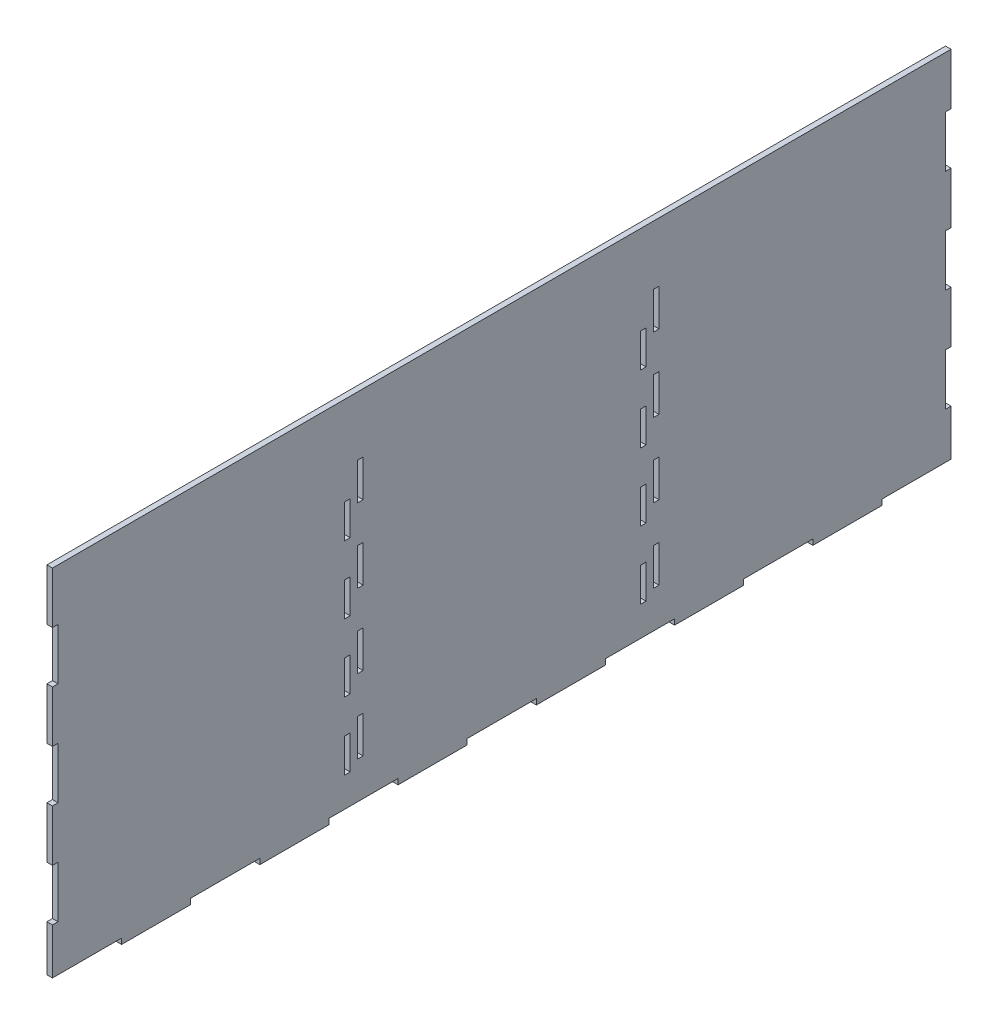
SolidWorks part; units mm, degrees
ref_plane "Front Plane" through (0, 0, 0) normal (0, 0, 1) x (1, 0, 0)
ref_plane "Top Plane" through (0, 0, 0) normal (0, 1, 0) x (1, 0, 0)
ref_plane "Right Plane" through (0, 0, 0) normal (1, 0, 0) x (0, 0, -1)
sketch "Sketch1" plane through (0, 0, 0) normal (1, 0, 0) x (0, 0, -1)
  line L0 (0, 152.4) -> (0, -152.4) construction
  line L1 (-381, 152.4) -> (381, 152.4)
  line L2 (-381, 152.4) -> (-381, -152.4)
  line L3 (-381, -152.4) -> (381, -152.4)
  line L4 (381, 152.4) -> (381, -152.4)
  line L5 (-381, 108.1768) -> (-381, 63.9536)
  line L10 (-381, 152.4) -> (-385.7625, 152.4)
  line L11 (-381, 152.4) -> (-381, 108.1768)
  line L12 (-381, 108.1768) -> (-385.7625, 108.1768)
  line L13 (-385.7625, 152.4) -> (-385.7625, 108.1768)
  line L14 (381, 152.4) -> (385.7625, 152.4)
  line L15 (381, 152.4) -> (381, 108.1768)
  line L16 (381, 108.1768) -> (385.7625, 108.1768)
  line L17 (385.7625, 152.4) -> (385.7625, 108.1768)
  line L18 (-385.7625, -152.4) -> (-326.4144, -152.4)
  line L19 (-385.7625, -152.4) -> (-385.7625, -157.1625)
  line L20 (-385.7625, -157.1625) -> (-326.4144, -157.1625)
  line L21 (-326.4144, -152.4) -> (-326.4144, -157.1625)
  line L22 (-381, 108.1768) -> (-385.7625, 108.1768)
  line L23 (-385.7625, 108.1768) -> (-385.7625, 63.9536)
  line L24 (-381, 63.9536) -> (-385.7625, 63.9536)
  line L25 (381, 108.1768) -> (381, 63.9536)
  line L26 (381, 108.1768) -> (385.7625, 108.1768)
  line L27 (385.7625, 108.1768) -> (385.7625, 63.9536)
  line L28 (381, 63.9536) -> (385.7625, 63.9536)
  line L29 (-381, 63.9536) -> (-381, 19.7304)
  line L30 (-381, 63.9536) -> (-385.7625, 63.9536)
  line L31 (-385.7625, 63.9536) -> (-385.7625, 19.7304)
  line L32 (-381, 19.7304) -> (-385.7625, 19.7304)
  line L33 (381, 63.9536) -> (381, 19.7304)
  line L34 (381, 63.9536) -> (385.7625, 63.9536)
  line L35 (385.7625, 63.9536) -> (385.7625, 19.7304)
  line L36 (381, 19.7304) -> (385.7625, 19.7304)
  line L37 (-381, 19.7304) -> (-381, -24.4929)
  line L38 (-381, 19.7304) -> (-385.7625, 19.7304)
  line L39 (-385.7625, 19.7304) -> (-385.7625, -24.4929)
  line L40 (-381, -24.4929) -> (-385.7625, -24.4929)
  line L41 (381, 19.7304) -> (381, -24.4929)
  line L42 (381, 19.7304) -> (385.7625, 19.7304)
  line L43 (385.7625, 19.7304) -> (385.7625, -24.4929)
  line L44 (381, -24.4929) -> (385.7625, -24.4929)
  line L45 (-381, -24.4929) -> (-381, -68.7161)
  line L46 (-381, -24.4929) -> (-385.7625, -24.4929)
  line L47 (-385.7625, -24.4929) -> (-385.7625, -68.7161)
  line L48 (-381, -68.7161) -> (-385.7625, -68.7161)
  line L49 (381, -24.4929) -> (381, -68.7161)
  line L50 (381, -24.4929) -> (385.7625, -24.4929)
  line L51 (385.7625, -24.4929) -> (385.7625, -68.7161)
  line L52 (381, -68.7161) -> (385.7625, -68.7161)
  line L53 (-381, -68.7161) -> (-381, -112.9393)
  line L54 (-381, -68.7161) -> (-385.7625, -68.7161)
  line L55 (-385.7625, -68.7161) -> (-385.7625, -112.9393)
  line L56 (-381, -112.9393) -> (-385.7625, -112.9393)
  line L57 (381, -68.7161) -> (381, -112.9393)
  line L58 (381, -68.7161) -> (385.7625, -68.7161)
  line L59 (385.7625, -68.7161) -> (385.7625, -112.9393)
  line L60 (381, -112.9393) -> (385.7625, -112.9393)
  line L61 (-381, -112.9393) -> (-381, -157.1625)
  line L62 (-381, -112.9393) -> (-385.7625, -112.9393)
  line L63 (-385.7625, -112.9393) -> (-385.7625, -157.1625)
  line L64 (-381, -157.1625) -> (-385.7625, -157.1625)
  line L65 (381, -112.9393) -> (381, -157.1625)
  line L66 (381, -112.9393) -> (385.7625, -112.9393)
  line L67 (385.7625, -112.9393) -> (385.7625, -157.1625)
  line L68 (381, -157.1625) -> (385.7625, -157.1625)
  line L69 (-326.4144, -157.1625) -> (-267.0663, -157.1625)
  line L70 (-326.4144, -152.4) -> (-326.4144, -157.1625)
  line L71 (-326.4144, -152.4) -> (-267.0663, -152.4)
  line L72 (-267.0663, -152.4) -> (-267.0663, -157.1625)
  line L73 (-267.0663, -157.1625) -> (-207.7183, -157.1625)
  line L74 (-267.0663, -152.4) -> (-267.0663, -157.1625)
  line L75 (-267.0663, -152.4) -> (-207.7183, -152.4)
  line L76 (-207.7183, -152.4) -> (-207.7183, -157.1625)
  line L77 (-207.7183, -157.1625) -> (-148.3702, -157.1625)
  line L78 (-207.7183, -152.4) -> (-207.7183, -157.1625)
  line L79 (-207.7183, -152.4) -> (-148.3702, -152.4)
  line L80 (-148.3702, -152.4) -> (-148.3702, -157.1625)
  line L81 (-148.3702, -157.1625) -> (-89.0221, -157.1625)
  line L82 (-148.3702, -152.4) -> (-148.3702, -157.1625)
  line L83 (-148.3702, -152.4) -> (-89.0221, -152.4)
  line L84 (-89.0221, -152.4) -> (-89.0221, -157.1625)
  line L85 (-89.0221, -157.1625) -> (-29.674, -157.1625)
  line L86 (-89.0221, -152.4) -> (-89.0221, -157.1625)
  line L87 (-89.0221, -152.4) -> (-29.674, -152.4)
  line L88 (-29.674, -152.4) -> (-29.674, -157.1625)
  line L89 (-29.674, -157.1625) -> (29.674, -157.1625)
  line L90 (-29.674, -152.4) -> (-29.674, -157.1625)
  line L91 (-29.674, -152.4) -> (29.674, -152.4)
  line L92 (29.674, -152.4) -> (29.674, -157.1625)
  line L93 (29.674, -157.1625) -> (89.0221, -157.1625)
  line L94 (29.674, -152.4) -> (29.674, -157.1625)
  line L95 (29.674, -152.4) -> (89.0221, -152.4)
  line L96 (89.0221, -152.4) -> (89.0221, -157.1625)
  line L97 (89.0221, -157.1625) -> (148.3702, -157.1625)
  line L98 (89.0221, -152.4) -> (89.0221, -157.1625)
  line L99 (89.0221, -152.4) -> (148.3702, -152.4)
  line L100 (148.3702, -152.4) -> (148.3702, -157.1625)
  line L101 (148.3702, -157.1625) -> (207.7183, -157.1625)
  line L102 (148.3702, -152.4) -> (148.3702, -157.1625)
  line L103 (148.3702, -152.4) -> (207.7183, -152.4)
  line L104 (207.7183, -152.4) -> (207.7183, -157.1625)
  line L105 (207.7183, -157.1625) -> (267.0663, -157.1625)
  line L106 (207.7183, -152.4) -> (207.7183, -157.1625)
  line L107 (207.7183, -152.4) -> (267.0663, -152.4)
  line L108 (267.0663, -152.4) -> (267.0663, -157.1625)
  line L125 (-124.6188, 0) -> (124.6188, 0) construction
  line L126 (-129.3812, 41.956) -> (-124.6188, 41.956) construction
  line L127 (-129.3812, 41.956) -> (-129.3812, -41.956) construction
  line L128 (-129.3812, -41.956) -> (-124.6188, -41.956) construction
  line L129 (-124.6188, 41.956) -> (-124.6188, -41.956) construction
  line L138 (124.6188, 41.956) -> (129.3813, 41.956) construction
  line L139 (124.6188, 41.956) -> (124.6188, -41.956) construction
  line L140 (124.6188, -41.956) -> (129.3813, -41.956) construction
  line L141 (129.3813, 41.956) -> (129.3813, -41.956) construction
  line L143 (267.0663, -157.1625) -> (326.4144, -157.1625)
  line L144 (267.0663, -152.4) -> (267.0663, -157.1625)
  line L145 (267.0663, -152.4) -> (326.4144, -152.4)
  line L146 (326.4144, -152.4) -> (326.4144, -157.1625)
  line L147 (326.4144, -157.1625) -> (385.7625, -157.1625)
  line L148 (326.4144, -152.4) -> (326.4144, -157.1625)
  line L149 (326.4144, -152.4) -> (385.7625, -152.4)
  line L150 (385.7625, -152.4) -> (385.7625, -157.1625)
  point P6 (0, 0)
  point P113 (-127, 41.956)
  point P114 (127, 41.956)
  point P117 (0, 0)
  dimension "D1" = 762
  dimension "D2" = 304.8
  dimension "D3" = 771.525
  dimension "D4" = 309.5625
  dimension "D5" = 44.2232
  dimension "D7" = 59.3481
  dimension "D9" = 254
  dimension "D10" = 4.7625
  dimension "D6" = 7
  dimension "D8" = 13
extrude "Boss-Extrude1" add sketch "Sketch1" along normal blind 4.7625 contours L0 L1 L2 L3 | L10 L13 L12 L2 | L32 L2 L24 L31 | L48 L2 L40 L47 | L56 L63 L18 L2 | L72 L3 L21 L69 | L80 L3 L76 L77 | L96 L3 L92 L93 | L3 L108 | L4 L67 L60 | L4 L52 L51 L44 | L4 L36 L35 L28 | L17 L14 L4 L16 | L88 L3 L84 L85 | L104 L3 L100 L101 region at (0, 0, 0) region at (0, 130.2884, 383.3813) region at (0, 130.2884, -383.3812) region at (0, 41.842, 383.3812) region at (0, 41.842, -383.3813) region at (0, -46.6045, 383.3812) region at (0, -46.6045, -383.3813) region at (0, -132.6696, 383.3812) region at (0, -132.6696, -383.3813) region at (0, -154.7813, 296.7404) region at (0, -154.7813, -296.7404) region at (0, -154.7813, 178.0442) region at (0, -154.7813, -178.0442) region at (0, -154.7813, 59.3481) region at (0, -154.7813, -59.3481)
sketch "Sketch3" plane through (4.7625, 0, 0) normal (1, 0, 0) x (0, 0, -1)
  line L0 (-130.175, -127) -> (-130.175, 76.2) construction
  line L5 (-134.9375, 76.2) -> (-130.175, 76.2)
  line L6 (-134.9375, 76.2) -> (-134.9375, 47.1714)
  line L7 (-134.9375, 47.1714) -> (-130.175, 47.1714)
  line L8 (-130.175, 76.2) -> (-130.175, 47.1714)
  line L9 (-119.0625, 101.6) -> (-123.825, 101.6)
  line L10 (-119.0625, 101.6) -> (-119.0625, 69.85)
  line L11 (-119.0625, 69.85) -> (-123.825, 69.85)
  line L12 (-123.825, 101.6) -> (-123.825, 69.85)
  line L13 (-381, -152.4) -> (381, -152.4) construction
  line L14 (-123.825, -152.4) -> (-123.825, 101.6) construction
  line L15 (-130.175, 76.2) -> (-123.825, 76.2) construction
  line L16 (-127, 41.956) -> (-127, 76.2) construction
  line L17 (-129.3812, 41.956) -> (-124.6188, 41.956) construction
  line L18 (-119.0625, 69.85) -> (-119.0625, 38.1)
  line L19 (-119.0625, 69.85) -> (-123.825, 69.85)
  line L20 (-123.825, 69.85) -> (-123.825, 38.1)
  line L21 (-119.0625, 38.1) -> (-123.825, 38.1)
  line L22 (-119.0625, 38.1) -> (-119.0625, 6.35)
  line L23 (-119.0625, 38.1) -> (-123.825, 38.1)
  line L24 (-123.825, 38.1) -> (-123.825, 6.35)
  line L25 (-119.0625, 6.35) -> (-123.825, 6.35)
  line L26 (-119.0625, 6.35) -> (-119.0625, -25.4)
  line L27 (-119.0625, 6.35) -> (-123.825, 6.35)
  line L28 (-123.825, 6.35) -> (-123.825, -25.4)
  line L29 (-119.0625, -25.4) -> (-123.825, -25.4)
  line L30 (-119.0625, -25.4) -> (-119.0625, -57.15)
  line L31 (-119.0625, -25.4) -> (-123.825, -25.4)
  line L32 (-123.825, -25.4) -> (-123.825, -57.15)
  line L33 (-119.0625, -57.15) -> (-123.825, -57.15)
  line L34 (-119.0625, -57.15) -> (-119.0625, -88.9)
  line L35 (-119.0625, -57.15) -> (-123.825, -57.15)
  line L36 (-123.825, -57.15) -> (-123.825, -88.9)
  line L37 (-119.0625, -88.9) -> (-123.825, -88.9)
  line L38 (-119.0625, -88.9) -> (-119.0625, -120.65)
  line L39 (-119.0625, -88.9) -> (-123.825, -88.9)
  line L40 (-123.825, -88.9) -> (-123.825, -120.65)
  line L41 (-119.0625, -120.65) -> (-123.825, -120.65)
  line L42 (-134.9375, 47.1714) -> (-134.9375, 18.1429)
  line L43 (-134.9375, 47.1714) -> (-130.175, 47.1714)
  line L44 (-130.175, 47.1714) -> (-130.175, 18.1429)
  line L45 (-134.9375, 18.1429) -> (-130.175, 18.1429)
  line L46 (-134.9375, 18.1429) -> (-134.9375, -10.8857)
  line L47 (-134.9375, 18.1429) -> (-130.175, 18.1429)
  line L48 (-130.175, 18.1429) -> (-130.175, -10.8857)
  line L49 (-134.9375, -10.8857) -> (-130.175, -10.8857)
  line L50 (-134.9375, -10.8857) -> (-134.9375, -39.9143)
  line L51 (-134.9375, -10.8857) -> (-130.175, -10.8857)
  line L52 (-130.175, -10.8857) -> (-130.175, -39.9143)
  line L53 (-134.9375, -39.9143) -> (-130.175, -39.9143)
  line L54 (-134.9375, -39.9143) -> (-134.9375, -68.9429)
  line L55 (-134.9375, -39.9143) -> (-130.175, -39.9143)
  line L56 (-130.175, -39.9143) -> (-130.175, -68.9429)
  line L57 (-134.9375, -68.9429) -> (-130.175, -68.9429)
  line L58 (-134.9375, -68.9429) -> (-134.9375, -97.9714)
  line L59 (-134.9375, -68.9429) -> (-130.175, -68.9429)
  line L60 (-130.175, -68.9429) -> (-130.175, -97.9714)
  line L61 (-134.9375, -97.9714) -> (-130.175, -97.9714)
  line L62 (-134.9375, -97.9714) -> (-134.9375, -127)
  line L63 (-134.9375, -97.9714) -> (-130.175, -97.9714)
  line L64 (-130.175, -97.9714) -> (-130.175, -127)
  line L65 (-134.9375, -127) -> (-130.175, -127)
  line L66 (-119.0625, -120.65) -> (-119.0625, -152.4)
  line L67 (-119.0625, -120.65) -> (-123.825, -120.65)
  line L68 (-123.825, -120.65) -> (-123.825, -152.4)
  line L69 (-119.0625, -152.4) -> (-123.825, -152.4)
  line L70 (119.0625, 76.2) -> (123.825, 76.2)
  line L71 (119.0625, 76.2) -> (119.0625, 47.1714)
  line L72 (119.0625, 47.1714) -> (123.825, 47.1714)
  line L73 (123.825, 76.2) -> (123.825, 47.1714)
  line L74 (134.9375, 101.6) -> (130.175, 101.6)
  line L75 (134.9375, 101.6) -> (134.9375, 69.85)
  line L76 (134.9375, 69.85) -> (130.175, 69.85)
  line L77 (130.175, 101.6) -> (130.175, 69.85)
  line L78 (134.9375, 69.85) -> (134.9375, 38.1)
  line L79 (134.9375, 69.85) -> (130.175, 69.85)
  line L80 (130.175, 69.85) -> (130.175, 38.1)
  line L81 (134.9375, 38.1) -> (130.175, 38.1)
  line L82 (134.9375, 38.1) -> (134.9375, 6.35)
  line L83 (134.9375, 38.1) -> (130.175, 38.1)
  line L84 (130.175, 38.1) -> (130.175, 6.35)
  line L85 (134.9375, 6.35) -> (130.175, 6.35)
  line L86 (134.9375, 6.35) -> (134.9375, -25.4)
  line L87 (134.9375, 6.35) -> (130.175, 6.35)
  line L88 (130.175, 6.35) -> (130.175, -25.4)
  line L89 (134.9375, -25.4) -> (130.175, -25.4)
  line L90 (134.9375, -25.4) -> (134.9375, -57.15)
  line L91 (134.9375, -25.4) -> (130.175, -25.4)
  line L92 (130.175, -25.4) -> (130.175, -57.15)
  line L93 (134.9375, -57.15) -> (130.175, -57.15)
  line L94 (134.9375, -57.15) -> (134.9375, -88.9)
  line L95 (134.9375, -57.15) -> (130.175, -57.15)
  line L96 (130.175, -57.15) -> (130.175, -88.9)
  line L97 (134.9375, -88.9) -> (130.175, -88.9)
  line L98 (134.9375, -88.9) -> (134.9375, -120.65)
  line L99 (134.9375, -88.9) -> (130.175, -88.9)
  line L100 (130.175, -88.9) -> (130.175, -120.65)
  line L101 (134.9375, -120.65) -> (130.175, -120.65)
  line L102 (119.0625, 47.1714) -> (119.0625, 18.1429)
  line L103 (119.0625, 47.1714) -> (123.825, 47.1714)
  line L104 (123.825, 47.1714) -> (123.825, 18.1429)
  line L105 (119.0625, 18.1429) -> (123.825, 18.1429)
  line L106 (119.0625, 18.1429) -> (119.0625, -10.8857)
  line L107 (119.0625, 18.1429) -> (123.825, 18.1429)
  line L108 (123.825, 18.1429) -> (123.825, -10.8857)
  line L109 (119.0625, -10.8857) -> (123.825, -10.8857)
  line L110 (119.0625, -10.8857) -> (119.0625, -39.9143)
  line L111 (119.0625, -10.8857) -> (123.825, -10.8857)
  line L112 (123.825, -10.8857) -> (123.825, -39.9143)
  line L113 (119.0625, -39.9143) -> (123.825, -39.9143)
  line L114 (119.0625, -39.9143) -> (119.0625, -68.9429)
  line L115 (119.0625, -39.9143) -> (123.825, -39.9143)
  line L116 (123.825, -39.9143) -> (123.825, -68.9429)
  line L117 (119.0625, -68.9429) -> (123.825, -68.9429)
  line L118 (119.0625, -68.9429) -> (119.0625, -97.9714)
  line L119 (119.0625, -68.9429) -> (123.825, -68.9429)
  line L120 (123.825, -68.9429) -> (123.825, -97.9714)
  line L121 (119.0625, -97.9714) -> (123.825, -97.9714)
  line L122 (119.0625, -97.9714) -> (119.0625, -127)
  line L123 (119.0625, -97.9714) -> (123.825, -97.9714)
  line L124 (123.825, -97.9714) -> (123.825, -127)
  line L125 (119.0625, -127) -> (123.825, -127)
  line L126 (134.9375, -120.65) -> (134.9375, -152.4)
  line L127 (134.9375, -120.65) -> (130.175, -120.65)
  line L128 (130.175, -120.65) -> (130.175, -152.4)
  line L129 (134.9375, -152.4) -> (130.175, -152.4)
  line L130 (123.825, -127) -> (123.825, 76.2) construction
  line L131 (130.175, -152.4) -> (130.175, 101.6) construction
  line L132 (123.825, 76.2) -> (130.175, 76.2) construction
  line L133 (127, 41.956) -> (127, 76.2) construction
  line L134 (124.6188, 41.956) -> (129.3813, 41.956) construction
  dimension "D1" = 203.2
  dimension "D2" = 254
  dimension "D4" = 6.35
  dimension "D5" = 4.7625
  dimension "D7" = 31.75
  dimension "D9" = 29.0286
  dimension "D6" = 8
  dimension "D8" = 7
  dimension "D10" = 2
extrude "Cut-Extrude1" cut sketch "Sketch3" against normal through all contours L41 L38 L37 L40 | L33 L30 L29 L32 | L25 L22 L21 L24 | L9 L12 L11 L10 | L8 L5 L6 L7 | L46 L49 L48 L45 | L54 L57 L56 L53 | L62 L65 L64 L61 | L74 L77 L76 L75 | L73 L70 L71 L72 | L85 L82 L81 L84 | L106 L109 L108 L105 | L93 L90 L89 L92 | L114 L117 L116 L113 | L101 L98 L97 L100 | L122 L125 L124 L121 region at (4.7625, 61.6857, 132.5563) region at (4.7625, 3.6286, 132.5563) region at (4.7625, -54.4286, 132.5563) region at (4.7625, -112.4857, 132.5563) region at (4.7625, 85.725, 121.4438) region at (4.7625, 22.225, 121.4437) region at (4.7625, -41.275, 121.4437) region at (4.7625, -104.775, 121.4437) region at (4.7625, 61.6857, -121.4438) region at (4.7625, 3.6286, -121.4438) region at (4.7625, -54.4286, -121.4437) region at (4.7625, -112.4857, -121.4437) region at (4.7625, 85.725, -132.5562) region at (4.7625, 22.225, -132.5563) region at (4.7625, -41.275, -132.5563) region at (4.7625, -104.775, -132.5563)
equation "\"Height\"= 12in"
equation "\"Depth\"= 7in"
equation "\"WallThickness\"= 0.1875in"
equation "\"FloorThickness\"= 0.1875in"
equation "\"D2@Sketch1\"=\"Height\""
equation "\"D3@Sketch1\"=\"D1@Sketch1\"+2*\"WallThickness\""
equation "\"D4@Sketch1\"=\"D2@Sketch1\"+\"FloorThickness\""
equation "\"D5@Sketch1\"=\"D4@Sketch1\"/7"
equation "\"D7@Sketch1\"=\"D3@Sketch1\"/\"D8@Sketch1\""
equation "\"D1@Boss-Extrude1\"=\"WallThickness\""
equation "\"Width\" = 30in"
equation "\"D4@Sketch3\"=\"WallThickness\"+(1/16in)"
equation "\"D5@Sketch3\"=\"WallThickness\""
equation "\"D7@Sketch3\"=\"D2@Sketch3\"/\"D6@Sketch3\""
equation "\"D9@Sketch3\"=\"D1@Sketch3\"/\"D8@Sketch3\""
equation "\"D10@Sketch1\"=\"WallThickness\""
equation "\"D1@Sketch1\"=\"Width\""
